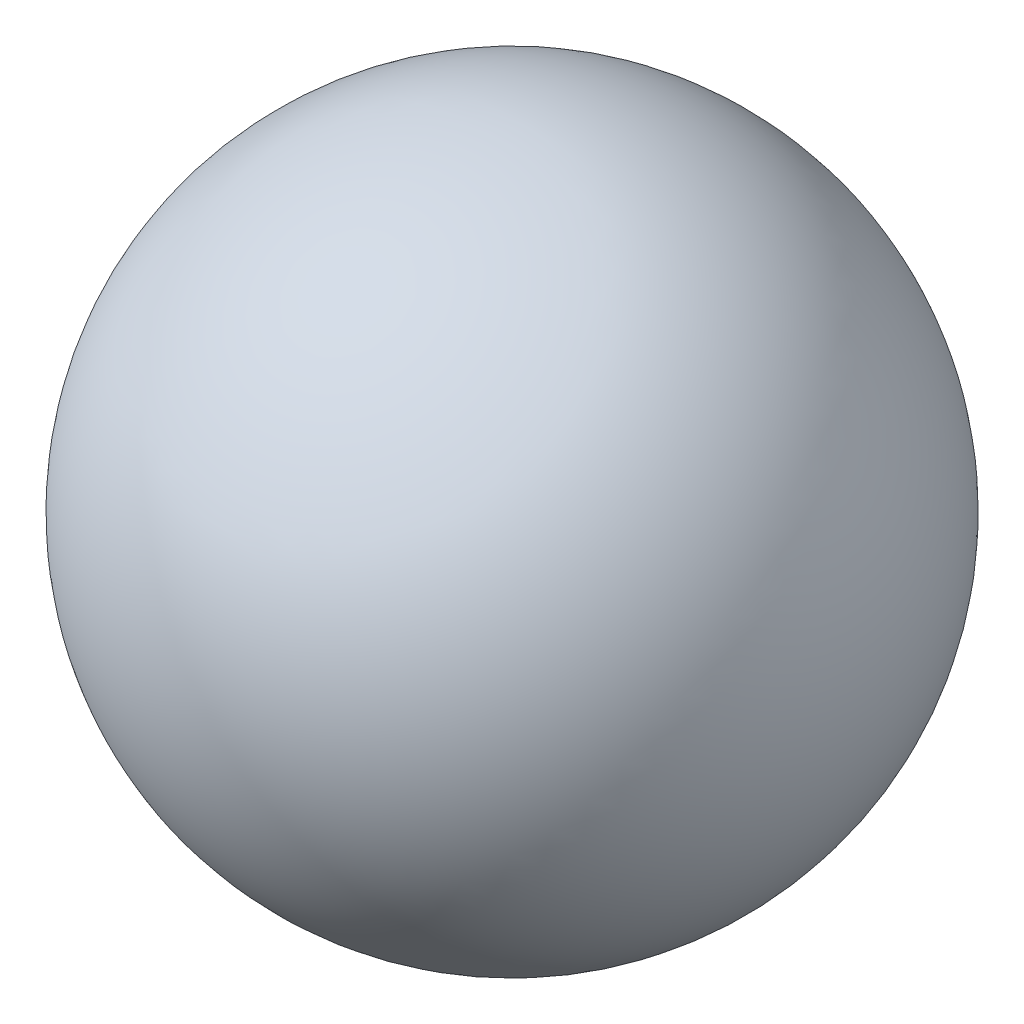
SolidWorks part; units mm, degrees
material "PLA"
ref_plane "Front Plane" through (0, 0, 0) normal (1, 0, 0) x (0, 1, 0)
ref_plane "Top Plane" through (0, 0, 0) normal (0, 0, 1) x (0, 1, 0)
ref_plane "Right Plane" through (0, 0, 0) normal (0, 1, 0) x (-1, 0, 0)
sketch "Sketch2" plane through (0, 0, 0) normal (1, 0, 0) x (0, 1, 0)
  line L0 (0, -15) -> (0, 15)
  arc A0 (0, 15) -> (0, -15) centre (0, 0) cw
  point P4 (0, 0)
  dimension "D1" = 30
revolve "Revolve1" add sketch "Sketch2" angle 360 about L0
equation "\"ball_diameter\"= 3cm"
equation "\"D1@Sketch2\"=\"ball_diameter\""
